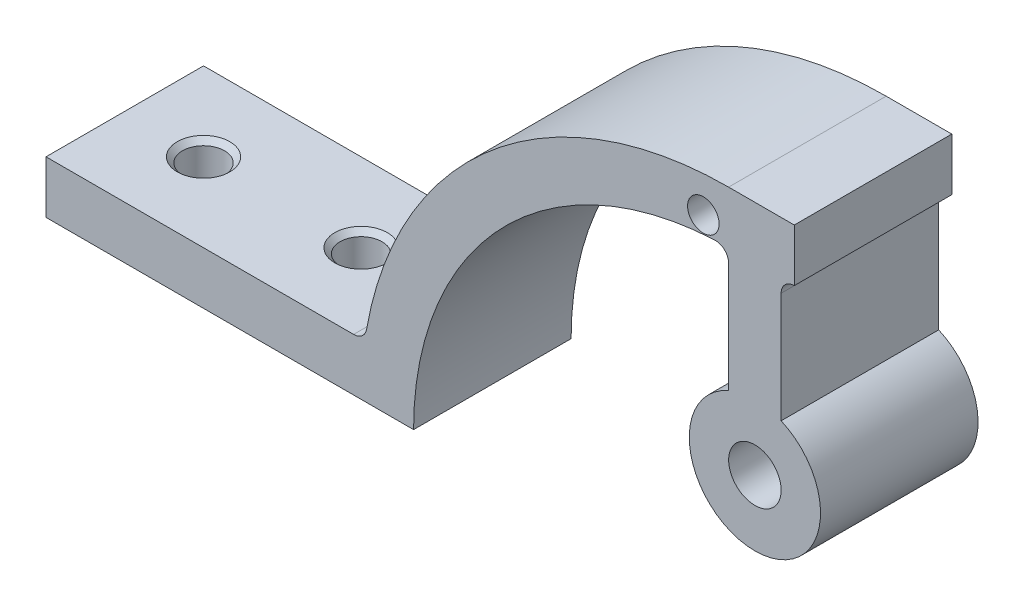
SolidWorks part; units mm, degrees
ref_plane "Front Plane" through (0, 0, 0) normal (0, 0, 1) x (1, 0, 0)
ref_plane "Top Plane" through (0, 0, 0) normal (0, 1, 0) x (1, 0, 0)
ref_plane "Right Plane" through (0, 0, 0) normal (1, 0, 0) x (0, 0, -1)
sketch "Sketch2" plane through (0, 0, 0) normal (0, 1, 0) x (1, 0, 0)
  line L0 (12.5, 7.5) -> (12.5, -7.5) construction
  line L1 (17.5, -7.5) -> (-17.5, -7.5)
  line L2 (17.5, -7.5) -> (17.5, 7.5)
  line L3 (17.5, 7.5) -> (-17.5, 7.5)
  line L4 (-17.5, -7.5) -> (-17.5, 7.5)
  line L5 (17.5, -7.5) -> (-17.5, 7.5) construction
  line L6 (17.5, 7.5) -> (-17.5, -7.5) construction
  circle A0 centre (-10, 0) radius 2
  circle A1 centre (5, 0) radius 2
  point P0 (0, 0)
  dimension "D5" = 4
  dimension "D6" = 4
  dimension "D1" = 15
  dimension "D2" = 35
  dimension "D3" = 15
  dimension "D4" = 10
  dimension "D7" = 5
extrude "Boss-Extrude1" add sketch "Sketch2" along normal blind 5
sketch "Sketch6" plane through (0, 0, 7.5) normal (0, 0, 1) x (1, 0, 0)
  line L0 (17.5, 0) -> (47.5, 0) construction
  line L1 (47.5, 0) -> (47.5, 30) construction
  line L2 (17.5, 0) -> (12.5, 0) construction
  line L4 (17.5, 0) -> (12.5, 0)
  line L5 (47.5, 35) -> (47.5, 33.8253) construction
  line L6 (47.5, 35) -> (52.5, 35)
  line L7 (47.5, 30) -> (47.5, 12.5)
  line L8 (47.5, 12.5) -> (52.5, 12.5)
  line L9 (52.5, 35) -> (52.5, 12.5)
  arc A0 (47.5, 35) -> (12.5, 0) centre (47.5, 0) ccw
  arc A1 (47.5, 30) -> (17.5, 0) centre (47.5, 0) ccw
  dimension "D1" = 70
  dimension "D2" = 60
  dimension "D3" = 5
  dimension "D4" = 22.5
extrude "Boss-Extrude6" add sketch "Sketch6" against normal blind 15
sketch "Sketch8" plane through (0, 0, 7.5) normal (0, 0, 1) x (1, 0, 0)
  line L0 (47.5, 12.5) -> (52.5, 12.5) construction
  circle A0 centre (50, 12.5) radius 6.25
  dimension "D1" = 12.5
extrude "Boss-Extrude7" add sketch "Sketch8" against normal blind 15
sketch "Sketch10" plane through (0, 0, 7.5) normal (0, 0, 1) x (1, 0, 0)
  circle A0 centre (50, 12.5) radius 2.5
  dimension "D1" = 5
extrude "Cut-Extrude1" cut sketch "Sketch10" against normal blind 15
chamfer "Chamfer1" distance 0.5 angle 45 2 edges at (5, 5, 2) (-10, 5, 2)
sketch "Sketch12" plane through (0, 0, 7.5) normal (0, 0, 1) x (1, 0, 0)
  line L1 (52.5, 35) -> (53.75, 35)
  line L2 (52.5, 35) -> (52.5, 30)
  line L3 (52.5, 30) -> (53.75, 30)
  line L4 (53.75, 35) -> (53.75, 30)
  dimension "D1" = 1.25
  dimension "D2" = 5
extrude "Boss-Extrude8" add sketch "Sketch12" against normal blind 15
fillet "Fillet2" radius 1.25 3 edges at (52.5, 30, 0) (47.5, 30, 0) (12.859, 5, 0)
sketch "Sketch16" plane through (0, 0, 7.5) normal (0, 0, 1) x (1, 0, 0)
  circle A0 centre (45.0915, 31.5) radius 1.5
  dimension "D1" = 3
  dimension "D2" = 3.5
extrude "Cut-Extrude3" cut sketch "Sketch16" against normal blind 15
